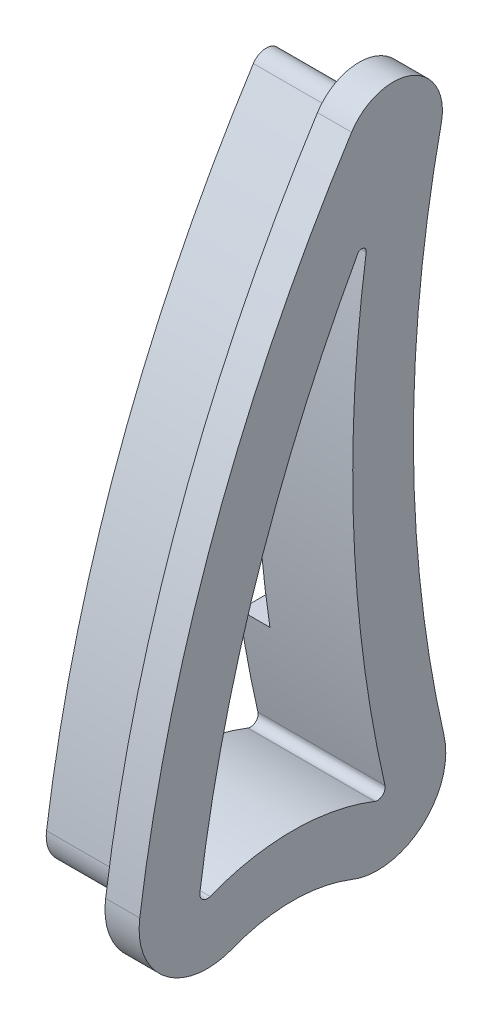
SolidWorks part; units mm, degrees
ref_plane "Front Plane" through (0, 0, 0) normal (0, 0, 1) x (1, 0, 0)
ref_plane "Top Plane" through (0, 0, 0) normal (0, 1, 0) x (1, 0, 0)
ref_plane "Right Plane" through (0, 0, 0) normal (1, 0, 0) x (0, 0, -1)
sketch "Sketch1" plane through (0, 0, 0) normal (0, 0, 1) x (1, 0, 0)
  line L0 (0, 0) -> (0, -27.8746) construction
  line L1 (-15.5575, 76.2) -> (15.5575, 76.2)
  line L2 (-15.5575, 76.2) -> (-15.5575, -76.2)
  line L3 (-15.5575, -76.2) -> (-7.8455, -76.2)
  line L4 (15.5575, 76.2) -> (15.5575, -76.2)
  line L5 (-15.5575, 76.2) -> (15.5575, -76.2) construction
  line L6 (-15.5575, -76.2) -> (15.5575, 76.2) construction
  line L7 (7.8455, -76.2) -> (9.525, -85.725)
  line L8 (-7.8455, -76.2) -> (-9.525, -85.725)
  line L9 (-9.525, -85.725) -> (9.525, -85.725)
  line L10 (7.8455, -76.2) -> (15.5575, -76.2)
  point P0 (0, 0)
  point P12 (0, -85.725)
  dimension "D1" = 31.115
  dimension "D2" = 152.4
  dimension "D3" = 20
  dimension "D4" = 19.05
  dimension "D5" = 9.525
extrude "Boss-Extrude1" add sketch "Sketch1" along normal blind 76.2
sketch "Sketch2" plane through (15.5575, 0, 0) normal (1, 0, 0) x (0, 0, -1)
  line L0 (-76.2, -76.2) -> (0, -76.2) construction
  line L1 (0, -85.725) -> (-6.985, -85.725)
  line L2 (0, -85.725) -> (0, -76.2)
  line L3 (0, -76.2) -> (-6.985, -76.2)
  line L4 (-6.985, -85.725) -> (-6.985, -76.2)
  dimension "D1" = 6.985
extrude "Cut-Extrude1" cut sketch "Sketch2" against normal through all
sketch "Sketch3" plane through (15.5575, 0, 0) normal (1, 0, 0) x (0, 0, -1)
  line L14 (-76.2, 76.2) -> (0, 76.2) construction
  line L15 (-76.2, -76.2) -> (-76.2, 76.2) construction
  line L16 (-76.2, -85.725) -> (-76.2, -76.2) construction
  line L17 (0, -76.2) -> (0, 76.2) construction
  line L18 (-76.2, -85.725) -> (-76.2, -76.2)
  line L19 (-76.2, -76.2) -> (-76.2, 76.2)
  line L20 (-76.2, 76.2) -> (-15.9075, 76.2)
  line L21 (0, -76.2) -> (0, 63.7964)
  arc A4 (-15.9075, 76.2) -> (-76.2, -85.725) centre (171.3838, -85.725) ccw
  arc A5 (0, 63.7964) -> (0, -76.2) centre (184.1989, -6.2018) ccw
  point P4 (-10.0952, 76.2)
  point P5 (0, 60.6261)
  point P6 (0, 50.0582)
  point P9 (-10.3594, 76.2)
  point P11 (0, 63.7964)
  point P12 (-15.9075, 76.2)
extrude "Cut-Extrude2" cut sketch "Sketch3" against normal through all
sketch "Sketch6" plane through (15.5575, 0, 0) normal (1, 0, 0) x (0, 0, -1)
  line L8 (-61.7469, -62.865) -> (-18.4126, -62.865)
  arc A2 (-26.0044, 40.4114) -> (-21.3821, 38.504) centre (-23.8641, 39.0437) cw
  arc A3 (-28.5756, -59.6454) -> (-20.9027, -53.058) centre (-26.4741, -54.3308) ccw
  arc A14 (-17.8942, 52.2835) -> (-61.7469, -62.865) centre (171.3838, -85.725) ccw
  arc A15 (-17.8942, 52.2835) -> (-18.4126, -62.865) centre (184.1989, -6.2018) ccw
  arc A16 (-26.0044, 40.4114) -> (-60.6442, -53.5457) centre (171.3838, -85.725) ccw
  arc A17 (-21.3821, 38.504) -> (-20.9027, -53.058) centre (184.1989, -6.2018) ccw
  arc A18 (-60.6442, -53.5457) -> (-52.8819, -59.6454) centre (-54.9834, -54.3308) ccw
  arc A19 (-52.8819, -59.6454) -> (-28.5756, -59.6454) centre (-40.7287, -90.3804) cw
  point P10 (0, 0)
  dimension "D2" = 2.54
  dimension "D3" = 5.715
  dimension "D1" = 13.335
extrude "Cut-Extrude3" cut sketch "Sketch6" against normal through all
sketch "Sketch7" plane through (0, 0, 0) normal (1, 0, 0) x (0, 0, -1)
  line L0 (-24.911, 16.933) -> (-11.489, 16.933)
  line L1 (-23.819, -37.677) -> (-10.3218, -37.677)
  arc A0 (0, 63.7964) -> (0, -76.2) centre (184.1989, -6.2018) ccw construction
  arc A1 (-21.3821, 38.504) -> (-20.9027, -53.058) centre (184.1989, -6.2018) ccw construction
  arc A2 (-24.911, 16.933) -> (-23.819, -37.677) centre (184.1989, -6.2018) ccw
  arc A3 (-11.489, 16.933) -> (-10.3218, -37.677) centre (184.1989, -6.2018) ccw
  point P3 (-12.8518, -6.2018)
  point P11 (0, 0)
  dimension "D1" = 54.61
extrude "Cut-Extrude4" cut sketch "Sketch7" against normal mid plane 10.16
sketch "Sketch9" plane through (15.5575, 0, 0) normal (1, 0, 0) x (0, 0, -1)
  line L0 (-15.9075, 76.2) -> (0, 63.7964)
ref_plane "Plane2" through (15.5575, 76.2, 15.9075) normal (0, -0.6149, -0.7886) x (-1, 0, 0)
sketch "Sketch10" plane through (15.5575, 76.2, 15.9075) normal (0, -0.6149, -0.7886) x (-1, 0, 0)
  line L4 (15.5575, 9.7815) -> (15.5575, 19.0294) construction
  line L5 (0, 9.7815) -> (31.115, 9.7815) construction
  line L6 (0, 9.7815) -> (8.255, 9.7815)
  line L7 (8.255, 9.7815) -> (0, -2.2835)
  line L8 (0, 0) -> (0, -110.402) construction
  line L9 (0, 9.7815) -> (0, -2.2835)
  line L10 (31.115, 9.7815) -> (31.115, -2.2835)
  line L11 (22.86, 9.7815) -> (31.115, -2.2835)
  line L12 (31.115, 9.7815) -> (22.86, 9.7815)
  point P2 (0, 0.955)
  dimension "D1" = 12.065
  dimension "D2" = 8.255
extrude "Cut-Extrude6" cut sketch "Sketch10" against normal mid plane 73.66
fillet "Fillet2" radius 0.762 5 edges at (-15.5575, 4.0516, 59.3496) (-14.7762, 75.3337, 16.653) (0, 76.2, 15.9075) (15.5575, 4.0516, 59.3496) (14.7762, 75.3337, 16.653)
sketch "Sketch11" plane through (15.5575, 0, 0) normal (1, 0, 0) x (0, 0, -1)
  arc A0 (-60.6442, -53.5457) -> (-52.8819, -59.6454) centre (-54.9834, -54.3308) ccw construction
  arc A1 (-28.5756, -59.6454) -> (-52.8819, -59.6454) centre (-40.7287, -90.3804) ccw construction
  arc A2 (-28.5756, -59.6454) -> (-20.9027, -53.058) centre (-26.4741, -54.3308) ccw construction
  arc A3 (-21.3821, 38.504) -> (-20.9027, -53.058) centre (184.1989, -6.2018) ccw construction
  arc A4 (-26.0044, 40.4114) -> (-60.6442, -53.5457) centre (171.3838, -85.725) ccw construction
  arc A5 (-21.3821, 38.504) -> (-26.0044, 40.4114) centre (-23.8641, 39.0437) ccw construction
  arc A6 (-60.6442, -53.5457) -> (-52.8819, -59.6454) centre (-54.9834, -54.3308) ccw
  arc A7 (-28.5756, -59.6454) -> (-52.8819, -59.6454) centre (-40.7287, -90.3804) ccw
  arc A8 (-28.5756, -59.6454) -> (-20.9027, -53.058) centre (-26.4741, -54.3308) ccw
  arc A9 (-21.3821, 38.504) -> (-20.9027, -53.058) centre (184.1989, -6.2018) ccw
  arc A10 (-26.0044, 40.4114) -> (-60.6442, -53.5457) centre (171.3838, -85.725) ccw
  arc A11 (-21.3821, 38.504) -> (-26.0044, 40.4114) centre (-23.8641, 39.0437) ccw
  arc A12 (-56.2413, -54.1563) -> (-54.5164, -55.5118) centre (-54.9834, -54.3308) ccw
  arc A13 (-26.9411, -55.5118) -> (-54.5164, -55.5118) centre (-40.7287, -90.3804) ccw
  arc A14 (-26.9411, -55.5118) -> (-25.236, -54.048) centre (-26.4741, -54.3308) ccw
  arc A15 (-27.7257, 29.0147) -> (-25.236, -54.048) centre (184.1989, -6.2018) ccw
  arc A16 (-27.7257, 29.0147) -> (-27.7257, 29.0147) centre (-27.7257, 29.0147) ccw
  arc A17 (-27.7257, 29.0147) -> (-56.2413, -54.1563) centre (171.3838, -85.725) ccw
  dimension "D1" = 4.445
extrude "Boss-Extrude2" add sketch "Sketch11" against normal blind 15.5575 separate body
fillet "Fillet3" radius 0.762 1 edges at (7.7787, 29.0147, 27.7257)
sketch "Sketch12" plane through (15.5575, 0, 0) normal (1, 0, 0) x (0, 0, -1)
  arc A28 (-56.2413, -54.1563) -> (-54.5164, -55.5118) centre (-54.9834, -54.3308) ccw construction
  arc A29 (-26.9411, -55.5118) -> (-54.5164, -55.5118) centre (-40.7287, -90.3804) ccw construction
  arc A30 (-26.9411, -55.5118) -> (-25.236, -54.048) centre (-26.4741, -54.3308) ccw construction
  arc A31 (-28.373, 24.8697) -> (-25.236, -54.048) centre (184.1989, -6.2018) ccw construction
  arc A32 (-29.794, 25.3482) -> (-56.2413, -54.1563) centre (171.3838, -85.725) ccw construction
  arc A33 (-28.373, 24.8697) -> (-29.794, 25.3482) centre (-29.127, 24.9799) ccw construction
  arc A34 (-56.2413, -54.1563) -> (-54.5164, -55.5118) centre (-54.9834, -54.3308) ccw
  arc A35 (-26.9411, -55.5118) -> (-54.5164, -55.5118) centre (-40.7287, -90.3804) ccw
  arc A36 (-26.9411, -55.5118) -> (-25.236, -54.048) centre (-26.4741, -54.3308) ccw
  arc A37 (-28.373, 24.8697) -> (-25.236, -54.048) centre (184.1989, -6.2018) ccw
  arc A38 (-29.794, 25.3482) -> (-56.2413, -54.1563) centre (171.3838, -85.725) ccw
  arc A39 (-28.373, 24.8697) -> (-29.794, 25.3482) centre (-29.127, 24.9799) ccw
  arc A52 (-30.8201, 43.4888) -> (-66.305, -52.7606) centre (171.3838, -85.725) ccw
  arc A53 (-66.305, -52.7606) -> (-50.7804, -64.96) centre (-54.9834, -54.3308) ccw
  arc A54 (-30.6771, -64.96) -> (-50.7804, -64.96) centre (-40.7287, -90.3804) ccw
  arc A55 (-30.6771, -64.96) -> (-15.3312, -51.7852) centre (-26.4741, -54.3308) ccw
  arc A56 (-15.7976, 37.2896) -> (-15.3312, -51.7852) centre (184.1989, -6.2018) ccw
  arc A57 (-15.7976, 37.2896) -> (-30.8201, 43.4888) centre (-23.8641, 39.0437) ccw
  arc A58 (-30.8201, 43.4888) -> (-66.305, -52.7606) centre (171.3838, -85.725) ccw
  arc A59 (-66.305, -52.7606) -> (-50.7804, -64.96) centre (-54.9834, -54.3308) ccw
  arc A60 (-30.6771, -64.96) -> (-50.7804, -64.96) centre (-40.7287, -90.3804) ccw
  arc A61 (-30.6771, -64.96) -> (-15.3312, -51.7852) centre (-26.4741, -54.3308) ccw
  arc A62 (-15.7976, 37.2896) -> (-15.3312, -51.7852) centre (184.1989, -6.2018) ccw
  arc A63 (-15.7976, 37.2896) -> (-30.8201, 43.4888) centre (-23.8641, 39.0437) ccw
  dimension "D1" = 5.715
extrude "Boss-Extrude3" add sketch "Sketch12" along normal blind 5.715
sketch "Sketch13" plane through (0, 0, 0) normal (1, 0, 0) x (0, 0, -1)
  line L0 (-11.489, 16.933) -> (-29.3825, 16.933)
  line L1 (-10.3218, -37.677) -> (-28.3136, -37.677)
  arc A0 (-28.373, 24.8697) -> (-25.236, -54.048) centre (184.1989, -6.2018) ccw construction
  arc A1 (-0.8368, 61.5534) -> (0, -76.2) centre (184.1989, -6.2018) ccw construction
  arc A2 (-29.3825, 16.933) -> (-28.3136, -37.677) centre (184.1989, -6.2018) ccw
  arc A3 (-11.489, 16.933) -> (-10.3218, -37.677) centre (184.1989, -6.2018) ccw
extrude "Cut-Extrude7" cut sketch "Sketch13" along normal blind 5.08
delete or keep bodies "Body-Delete/Keep 1" type delete bodies bodies 107
combine bodies "Combine1" operation type add bodies to combine 111 109
